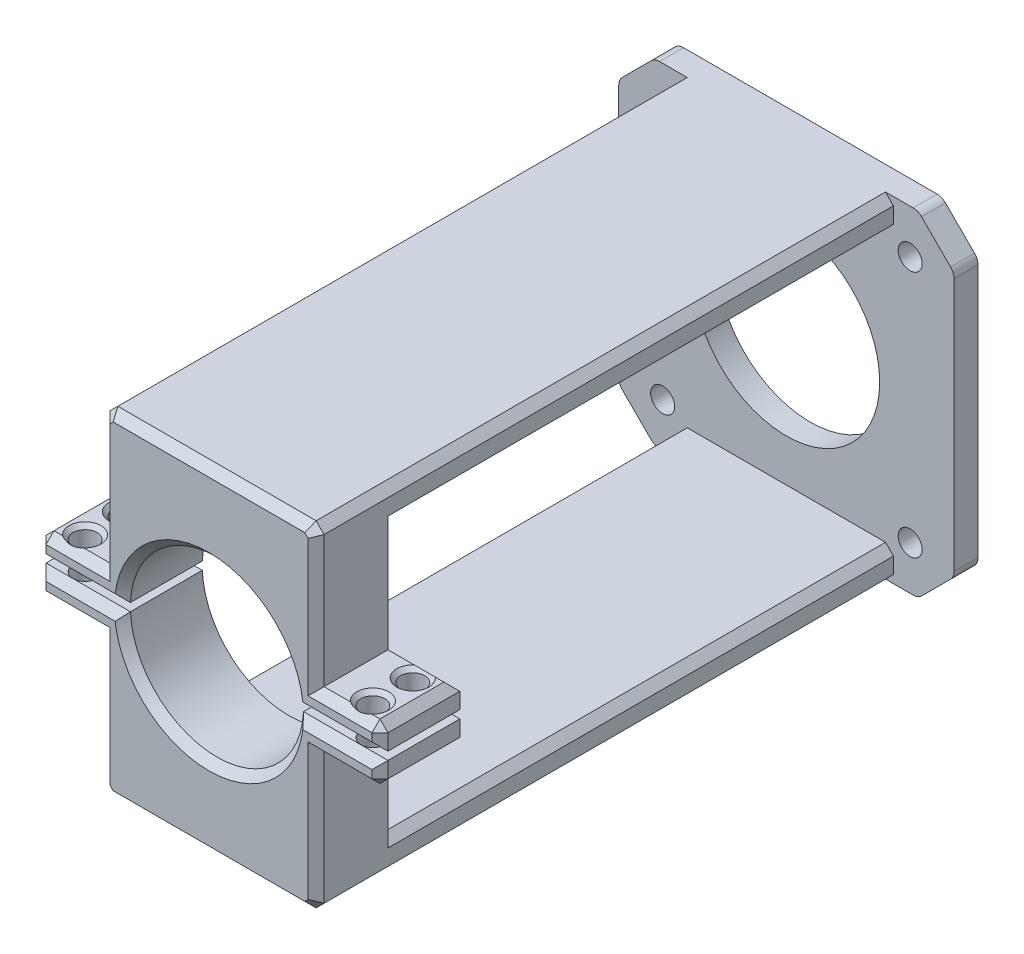
SolidWorks part; units mm, degrees
ref_plane "Front Plane" through (0, 0, 0) normal (0, 0, 1) x (1, 0, 0)
ref_plane "Top Plane" through (0, 0, 0) normal (0, 1, 0) x (1, 0, 0)
ref_plane "Right Plane" through (0, 0, 0) normal (1, 0, 0) x (0, 0, -1)
sketch "Sketch1" plane through (0, 0, 0) normal (0, 0, 1) x (1, 0, 0)
  line L0 (20.5607, 16.9393) -> (16.9393, 20.5607) construction
  line L1 (-20.5607, -16.9393) -> (-16.9393, -20.5607) construction
  line L2 (-15.8787, -21) -> (15.8787, -21) construction
  line L3 (16.9393, -20.5607) -> (20.5607, -16.9393) construction
  line L4 (21, -15.8787) -> (21, 15.8787) construction
  line L5 (-21, 15.8787) -> (-21, -15.8787) construction
  line L6 (15.8787, 21) -> (-15.8787, 21) construction
  line L7 (-16.9393, 20.5607) -> (-20.5607, 16.9393) construction
  line L8 (20.5607, 16.9393) -> (16.9393, 20.5607)
  line L9 (-20.5607, -16.9393) -> (-16.9393, -20.5607)
  line L10 (-15.8787, -21) -> (15.8787, -21)
  line L11 (16.9393, -20.5607) -> (20.5607, -16.9393)
  line L12 (21, -15.8787) -> (21, 15.8787)
  line L13 (-21, 15.8787) -> (-21, -15.8787)
  line L14 (15.8787, 21) -> (-15.8787, 21)
  line L15 (-16.9393, 20.5607) -> (-20.5607, 16.9393)
  circle A0 centre (-15.5, 15.5) radius 1.5
  circle A1 centre (15.5, 15.5) radius 1.5
  circle A2 centre (15.5, -15.5) radius 1.5
  circle A3 centre (-15.5, -15.5) radius 1.5
  arc A4 (-21, -15.8787) -> (-20.5607, -16.9393) centre (-19.5, -15.8787) ccw construction
  arc A5 (-16.9393, -20.5607) -> (-15.8787, -21) centre (-15.8787, -19.5) ccw construction
  arc A6 (15.8787, -21) -> (16.9393, -20.5607) centre (15.8787, -19.5) ccw construction
  arc A7 (20.5607, -16.9393) -> (21, -15.8787) centre (19.5, -15.8787) ccw construction
  arc A8 (21, 15.8787) -> (20.5607, 16.9393) centre (19.5, 15.8787) ccw construction
  arc A9 (16.9393, 20.5607) -> (15.8787, 21) centre (15.8787, 19.5) ccw construction
  arc A10 (-20.5607, 16.9393) -> (-21, 15.8787) centre (-19.5, 15.8787) ccw construction
  arc A11 (-15.8787, 21) -> (-16.9393, 20.5607) centre (-15.8787, 19.5) ccw construction
  arc A12 (-21, -15.8787) -> (-20.5607, -16.9393) centre (-19.5, -15.8787) ccw
  arc A13 (-16.9393, -20.5607) -> (-15.8787, -21) centre (-15.8787, -19.5) ccw
  arc A14 (15.8787, -21) -> (16.9393, -20.5607) centre (15.8787, -19.5) ccw
  arc A15 (20.5607, -16.9393) -> (21, -15.8787) centre (19.5, -15.8787) ccw
  arc A16 (21, 15.8787) -> (20.5607, 16.9393) centre (19.5, 15.8787) ccw
  arc A17 (16.9393, 20.5607) -> (15.8787, 21) centre (15.8787, 19.5) ccw
  arc A18 (-20.5607, 16.9393) -> (-21, 15.8787) centre (-19.5, 15.8787) ccw
  arc A19 (-15.8787, 21) -> (-16.9393, 20.5607) centre (-15.8787, 19.5) ccw
  circle A20 centre (0, 0) radius 11.6831
  point P12 (0, 0)
  dimension "D1" = 4
extrude "Boss-Extrude1" add sketch "Sketch1" along normal blind 3
sketch "Sketch2" plane through (0, 0, 3) normal (0, 0, 1) x (1, 0, 0)
  line L0 (13.4163, -21) -> (-13.4163, -21)
  line L1 (-15.8787, -21) -> (15.8787, -21) construction
  line L2 (-13.4163, -21) -> (-13.4163, -17)
  line L3 (-13.4163, -17) -> (13.4163, -17)
  line L4 (13.4163, -17) -> (13.4163, -21)
  line L5 (0, 0) -> (18.7181, 0)
  line L6 (13.4163, 17) -> (13.4163, 21)
  line L7 (-13.4163, 17) -> (13.4163, 17)
  line L8 (-13.4163, 21) -> (-13.4163, 17)
  line L9 (13.4163, 21) -> (-13.4163, 21)
  point P5 (0, -21)
  point P14 (0, 21)
  line M8 (15.8787, 21) -> (-15.8787, 21)
  line M16 (-15.8787, -21) -> (15.8787, -21)
  dimension "D1" = 4
extrude "Boss-Extrude2" add sketch "Sketch2" along normal up to surface (70.3215 mm away) contours L4 L3 L2 M16 | L8 L7 L6 M8 region at (0, -19, 3) region at (0, 19, 3)
sketch "Sketch3" plane through (0, 0, 73.3215) normal (0, 0, 1) x (1, 0, 0)
  line L0 (13.4163, 3.5) -> (13.4163, 21)
  line L1 (13.4163, -21) -> (-13.4163, -21)
  line L2 (13.4163, -21) -> (13.4163, -3.5)
  line L3 (13.4163, 21) -> (-13.4163, 21)
  line L4 (-13.4163, -21) -> (-13.4163, -3.5)
  line L5 (21.4163, 0.5) -> (13.4163, 0.5)
  line L6 (21.4163, -0.5) -> (10.8377, -0.5)
  line L7 (21.4163, -0.5) -> (13.4163, -0.5)
  line L8 (21.4163, -0.5) -> (21.4163, -3.5)
  line L9 (21.4163, -3.5) -> (13.4163, -3.5)
  line L11 (21.4163, 0.5) -> (13.4163, 0.5)
  line L12 (21.4163, 0.5) -> (21.4163, 3.5)
  line L13 (21.4163, 3.5) -> (13.4163, 3.5)
  line L16 (0, 0) -> (0, 13.4981)
  line L17 (-21.4163, 3.5) -> (-13.4163, 3.5)
  line L18 (-21.4163, 0.5) -> (-21.4163, 3.5)
  line L19 (-21.4163, 0.5) -> (-13.4163, 0.5)
  line L20 (-21.4163, -3.5) -> (-13.4163, -3.5)
  line L21 (-21.4163, -0.5) -> (-21.4163, -3.5)
  line L22 (-21.4163, -0.5) -> (-13.4163, -0.5)
  line L23 (-21.4163, -0.5) -> (-10.8377, -0.5)
  line L24 (-21.4163, 0.5) -> (-10.8377, 0.5)
  line L25 (-13.4163, 3.5) -> (-13.4163, 21)
  line L26 (-10.8377, 0.5) -> (-21.4163, 0.5)
  line L27 (10.8377, 0.5) -> (21.4163, 0.5)
  line L28 (-10.8377, -0.5) -> (-21.4163, -0.5)
  line L29 (10.8377, -0.5) -> (21.4163, -0.5)
  arc A0 (10.8377, 0.5) -> (-10.8377, 0.5) centre (0, 0) ccw
  arc A1 (-10.8377, -0.5) -> (10.8377, -0.5) centre (0, 0) ccw
  point P10 (-13.4163, -0.5)
  point P11 (-21.4163, -0.5)
  point P12 (0, 0)
  point P16 (13.4163, -0.5)
  point P17 (21.4163, -0.5)
  line M5 (13.4163, -21) -> (13.4163, -17)
  line M6 (13.4163, -17) -> (-13.4163, -17)
  line M7 (-13.4163, -17) -> (-13.4163, -21)
  line M8 (-13.4163, -21) -> (13.4163, -21)
  dimension "D1" = 8
  dimension "D2" = 8
  dimension "D3" = 3
  dimension "D4" = 3
extrude "Boss-Extrude3" add sketch "Sketch3" along normal blind 2 and the other way blind 8 contours A1 L23 L22 L21 L20 L4 L2 L9 L8 L6 M6 | M8 M5 M6 M7 | A0 L27 L5 L12 L13 L0 L3 L25 L17 L18 L19 L24 region at (17.4163, 3.0251, 73.3215) region at (0, -19, 73.3215) region at (0, -16.541, 73.3215)
sketch "Sketch4" plane through (0, -3.5, 0) normal (0, -1, 0) x (1, 0, 0)
  line L0 (0, 0) -> (0, 108.8223)
  line L2 (-15.8787, 0) -> (15.8787, 0) construction
  circle A0 centre (-18.0232, 72.8215) radius 1.5
  circle A1 centre (-18.0232, 67.8215) radius 1.5
  circle A2 centre (18.0232, 67.8215) radius 1.5
  circle A3 centre (18.0232, 72.8215) radius 1.5
  dimension "D1" = 3
  dimension "D2" = 3
extrude "Cut-Extrude1" cut sketch "Sketch4" against normal blind 20 contours A0 | A1 | A3 | A2 region at (-18.0232, -3.5, 72.8215) region at (-18.0232, -3.5, 67.8215) region at (18.0232, -3.5, 67.8215) region at (18.0232, -3.5, 72.8215)
chamfer "Chamfer1" distance 1 angle 45 8 edges at (-13.4163, -17, 34.1607) (-13.4163, -21, 39.1607) (13.4163, -21, 39.1607) (13.4163, -17, 34.1607) (13.4163, 17, 34.1607) (13.4163, 21, 39.1607) (-13.4163, 17, 34.1607) (-13.4163, 21, 39.1607)
chamfer "Chamfer2" distance 1 angle 45 34 edges at (-17.4163, -3.5, 75.3215) (-13.4163, -10.75, 65.3215) (-17.4163, -3.5, 65.3215) (-21.4163, -3.5, 70.3215) (-21.4163, -2, 75.3215) (-16.127, -0.5, 75.3215) (0, -10.8492, 75.3215) (16.127, -0.5, 75.3215) (21.4163, -2, 75.3215) (-13.4163, -11.75, 75.3215) (-12.9163, -20.5, 75.3215) (0, -21, 75.3215) (12.9163, -20.5, 75.3215) (13.4163, -11.75, 75.3215) (17.4163, -3.5, 75.3215) (17.4163, -3.5, 65.3215) (21.4163, -3.5, 70.3215) (17.4163, 3.5, 75.3215) (17.4163, 3.5, 65.3215) (21.4163, 3.5, 70.3215) (21.4163, 2, 75.3215) (16.127, 0.5, 75.3215) (0, 10.8492, 75.3215) (-16.127, 0.5, 75.3215) (-21.4163, 2, 75.3215) (-13.4163, 10.75, 65.3215) (-17.4163, 3.5, 65.3215) (-21.4163, 3.5, 70.3215) (-17.4163, 3.5, 75.3215) (-13.4163, 11.75, 75.3215) (-12.9163, 20.5, 75.3215) (13.4163, 11.75, 75.3215) (12.9163, 20.5, 75.3215) (0, 21, 75.3215)
chamfer "Chamfer3" distance 1 angle 45 2 edges at (13.4163, 10.25, 65.3215) (13.4163, -10.25, 65.3215)
chamfer "Chamfer4" distance 0.5 angle 45 8 edges at (-16.5232, 3.5, 67.8215) (-16.5232, 3.5, 72.8215) (-16.5232, -3.5, 67.8215) (-16.5232, -3.5, 72.8215) (19.5232, -3.5, 72.8215) (19.5232, -3.5, 67.8215) (16.5232, 3.5, 67.8215) (16.5232, 3.5, 72.8215)
